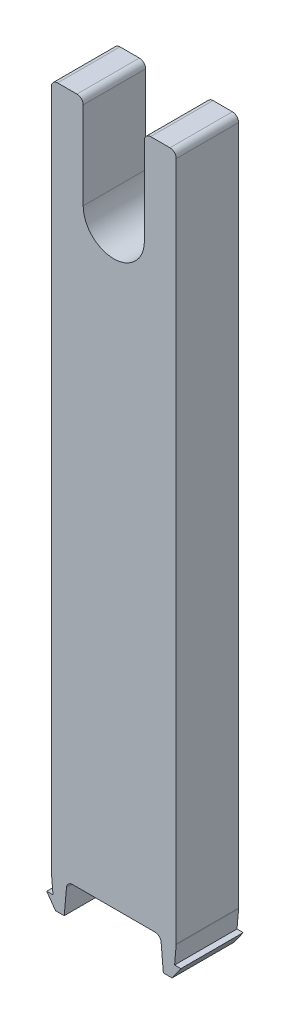
SolidWorks part; units mm, degrees
ref_plane "Front Plane" through (0, 0, 0) normal (0, 0, 1) x (1, 0, 0)
ref_plane "Top Plane" through (0, 0, 0) normal (0, 1, 0) x (1, 0, 0)
ref_plane "Right Plane" through (0, 0, 0) normal (1, 0, 0) x (0, 0, -1)
sketch "Sketch2" plane through (0, 0, 0) normal (0, 1, 0) x (1, 0, 0)
  line L1 (10, -5) -> (-10, -5)
  line L2 (10, -5) -> (10, 5)
  line L3 (10, 5) -> (-10, 5)
  line L4 (-10, -5) -> (-10, 5)
  line L5 (10, -5) -> (-10, 5) construction
  line L6 (10, 5) -> (-10, -5) construction
  point P0 (0, 0)
  point P6 (0, 0)
  dimension "D1" = 10
  dimension "D2" = 20
extrude "Boss-Extrude1" add sketch "Sketch2" along normal blind 110
sketch "Sketch3" plane through (0, 0, 5) normal (0, 0, 1) x (1, 0, 0)
  line L0 (-4.9, 110) -> (-4.9, 95)
  line L1 (-10, 110) -> (10, 110) construction
  line L2 (4.9, 95) -> (4.9, 110)
  line L3 (4.9, 110) -> (-4.9, 110)
  line L4 (-10, 0) -> (10, 0) construction
  arc A0 (-4.9, 95) -> (4.9, 95) centre (0, 95) ccw
  point P9 (0, 95)
  dimension "D2" = 4.9
  dimension "D1" = 95
extrude "Cut-Extrude1" cut sketch "Sketch3" against normal up to surface (10 mm away) up to face at (0, 55, -5)
sketch "Sketch4" plane through (0, 0, 5) normal (0, 0, 1) x (1, 0, 0)
  line L0 (-10, 0) -> (-7.5, 0)
  line L1 (-10, 0) -> (10, 0) construction
  line L2 (-7.5, 0) -> (-7.9374, -5)
  line L3 (-7.9374, -5) -> (-9.3373, -5)
  line L7 (-9.3373, -5) -> (-10.7375, -3)
  line L8 (-10.7375, -3) -> (-9.7375, -3)
  line L9 (-9.7375, -3) -> (-10, 0)
  dimension "D1" = 5
  dimension "D2" = 2
  dimension "D3" = 1
  dimension "D4" = 95
  dimension "D5" = 95
  dimension "D6" = 2.5
  dimension "D7" = 124.997
extrude "Boss-Extrude2" add sketch "Sketch4" against normal up to surface (10 mm away) up to face at (0, 78.1375, -5)
mirror "Mirror1" about plane through (0, 0, 0) normal (1, 0, 0) of "Boss-Extrude2"
fillet "Fillet1" radius 1 8 edges at (10, 110, 0) (4.9, 110, 0) (-4.9, 110, 0) (-10, 110, 0) (10, 0, 0) (7.5, 0, 0) (-7.5, 0, 0) (-10, 0, 0)
